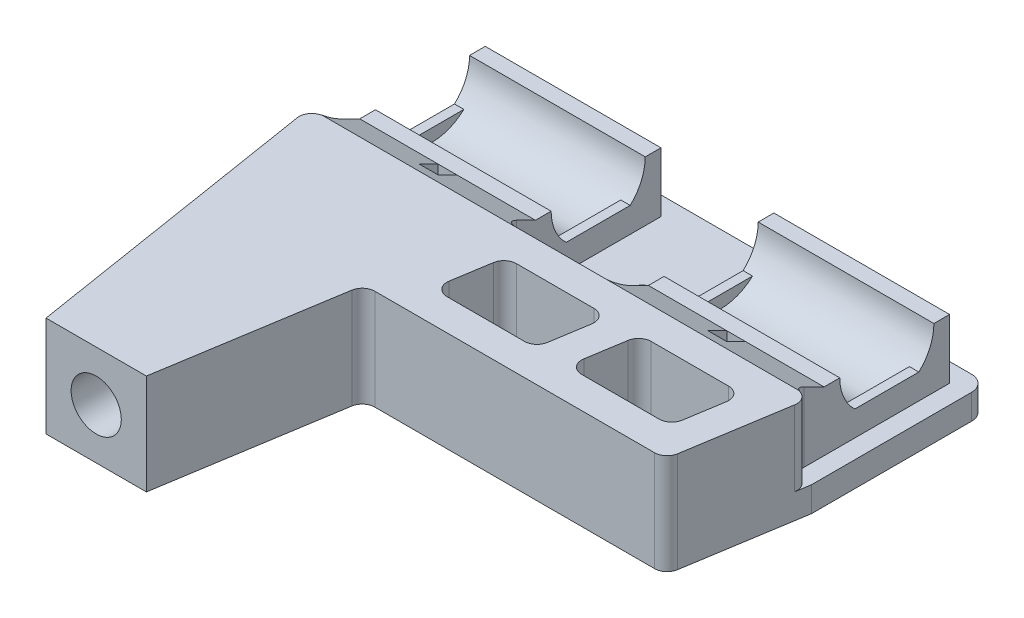
SolidWorks part; units mm, degrees
ref_plane "Front Plane" through (0, 0, 0) normal (0, 0, 1) x (1, 0, 0)
ref_plane "Top Plane" through (0, 0, 0) normal (0, 1, 0) x (1, 0, 0)
ref_plane "Right Plane" through (0, 0, 0) normal (1, 0, 0) x (0, 0, -1)
sketch "Sketch7" plane through (0, 0, 0) normal (0, 1, 0) x (1, 0, 0)
  line L0 (-40, 9) -> (40, 9)
  line L1 (-40, 37) -> (40, 37)
  line L2 (-40, 37) -> (-40, 9)
  line L3 (40, 9) -> (40, 37)
extrude "Extrude2" add sketch "Sketch7" along normal blind 4
sketch "Sketch8" plane through (0, 4, 0) normal (0, 1, 0) x (1, 0, 0)
  line L0 (-40, 66.843) -> (47.0843, 66.843)
  line L1 (-40, 37) -> (-40, 9) construction
  line L3 (-40, 14) -> (46, 14)
  line L4 (-40, 34) -> (46, 34)
  line L5 (-37, 34) -> (-37, 14)
  line L6 (-9, 34) -> (-9, 14)
  line L7 (9, 34) -> (9, 14)
  line L8 (37, 34) -> (37, 14)
extrude "Extrude3" add sketch "Sketch8" along normal blind 9.5 separate body contours L6 region at (-23, 4, -24)
sketch "Sketch10" plane through (-9, 0, 0) normal (1, 0, 0) x (0, 0, -1)
  line L0 (34, 13.5) -> (14, 13.5) construction
  line L1 (24, 13.5) -> (49.4193, 500000)
  line L4 (29.099, 8) -> (18.901, 8)
  circle A0 centre (24, 13.5) radius 7.5
  line M3 (34, 13.5) -> (14, 13.5)
extrude "Extrude6" cut sketch "Sketch10" against normal blind 28 contours A0 L4 M3 region at (-9, 10.906, -24)
ref_plane "Plane3" through (-35.5, 0, 0) normal (-1, 0, 0) x (0, 0, 1)
sketch "Sketch15" plane through (-35.5, 0, 0) normal (-1, 0, 0) x (0, 0, 1)
  circle A0 centre (-24, 13.5) radius 7.5
extrude "Extrude7" cut sketch "Sketch15" against normal blind 25
sketch "Sketch16" plane through (0, 0, -14) normal (0, 0, 1) x (1, 0, 0)
  line L0 (-37, 4) -> (-9, 4) construction
  line L1 (-24.5, 4) -> (-21.5, 4)
  line L3 (-21.5, 7) -> (-21.5, 4)
  line L4 (-21.5, 7) -> (-24.5, 7)
  line L5 (-24.5, 7) -> (-24.5, 4)
ref_plane "Plane4" through (-23, 0, 0) normal (1, 0, 0) x (0, 0, -1)
sketch "Sketch17" plane through (-23, 0, 0) normal (1, 0, 0) x (0, 0, -1)
  circle A0 centre (24, 13.5) radius 12.8062
sweep "Cut-Sweep1" cut profiles "Sketch16" path "Sketch17"
extrude "Extrude8" add sketch "Sketch8<4>" along normal blind 9.5 contours L8 L4 L7 L3 region at (23, 4, -24)
sketch "Sketch8<4>" plane through (0, 4, 0) normal (0, 1, 0) x (1, 0, 0) same geometry as "Sketch8"
sketch "Sketch18" plane through (37, 0, 0) normal (1, 0, 0) x (0, 0, -1)
  line L0 (34, 13.5) -> (14, 13.5) construction
  line L3 (29.099, 8) -> (18.901, 8)
  circle A0 centre (24, 13.5) radius 7.5
  line M3 (34, 13.5) -> (14, 13.5)
extrude "Extrude9" cut sketch "Sketch18" against normal blind 28 contours A0 L3 M3 region at (37, 10.906, -24)
ref_plane "Plane5" through (35.5, 0, 0) normal (1, 0, 0) x (0, 0, -1)
sketch "Sketch19" plane through (35.5, 0, 0) normal (1, 0, 0) x (0, 0, -1)
  circle A0 centre (24, 13.5) radius 7.5
extrude "Extrude10" cut sketch "Sketch19" against normal blind 25
sketch "Sketch20" plane through (0, 0, -14) normal (0, 0, 1) x (1, 0, 0)
  line L0 (21.5, 7) -> (24.5, 7)
  line L1 (9, 4) -> (37, 4) construction
  line L3 (24.5, 7) -> (24.5, 4)
  line L4 (24.5, 4) -> (21.5, 4)
  line L5 (21.5, 4) -> (21.5, 7)
ref_plane "Plane6" through (23, 0, 0) normal (1, 0, 0) x (0, 0, -1)
sketch "Sketch21" plane through (23, 0, 0) normal (1, 0, 0) x (0, 0, -1)
  circle A0 centre (24, 13.5) radius 12.8062
sweep "Cut-Sweep2" cut profiles "Sketch20" path "Sketch21"
fillet "Fillet1" radius 2.5 2 edges at (40, 2, -37) (-40, 2, -37)
sketch "Sketch22" plane through (0, 0, 0) normal (0, 1, 0) x (1, 0, 0)
  line L0 (36.785, -11.0939) -> (40, 9)
  line L1 (12.6682, 4) -> (11.0532, -6.0939)
  line L2 (17.7318, 4) -> (34.1364, 4)
  line L3 (32.5214, -6.0939) -> (16.1168, -6.0939)
  line L4 (40, 9) -> (-40, 9)
  line L5 (-3.7364, 4) -> (-5.3514, -6.0939)
  line L7 (-40, 9) -> (-32, -41)
  line L9 (17.7318, 4) -> (16.1168, -6.0939)
  line L16 (34.1364, 4) -> (32.5214, -6.0939)
  line L17 (-32, -41) -> (-16, -41)
  line L18 (-3.7364, 4) -> (12.6682, 4)
  line L19 (-11.215, -11.0939) -> (36.785, -11.0939)
  line L20 (-16, -41) -> (-11.215, -11.0939)
  line L21 (-5.3514, -6.0939) -> (11.0532, -6.0939)
extrude "Extrude11" add sketch "Sketch22" along normal blind 16
sketch "Sketch25" plane through (0, 4, 0) normal (0, 1, 0) x (-1, 0, 0)
  line L0 (-40, -9) -> (40, -9) construction
  line L1 (37, -14) -> (9, -14)
  line L2 (37, -14) -> (37, -9)
  line L3 (37, -9) -> (9, -9)
  line L4 (9, -14) -> (9, -9)
extrude "Extrude13" add sketch "Sketch25" along normal blind 12
sketch "Sketch26" plane through (-37, 0, 0) normal (-1, 0, 0) x (0, 0, 1)
  line L0 (-14, 13.5) -> (-9, 16)
  line L1 (-9, 16) -> (-14, 16)
  line L2 (-14, 16) -> (-14, 13.5)
extrude "Extrude14" cut sketch "Sketch26" against normal up to next
fillet "Fillet11" radius 2 1 edges at (-9, 10, -9)
sketch "Sketch27" plane through (0, 4, 0) normal (0, 1, 0) x (-1, 0, 0)
  line L1 (-37, -14) -> (-9, -14)
  line L2 (-37, -14) -> (-37, -9)
  line L3 (-37, -9) -> (-9, -9)
  line L4 (-9, -14) -> (-9, -9)
extrude "Extrude15" add sketch "Sketch27" along normal blind 12
sketch "Sketch28" plane through (37, 0, 0) normal (1, 0, 0) x (0, 0, -1)
  line L0 (14, 13.5) -> (9, 16)
  line L1 (9, 16) -> (14, 16)
  line L2 (14, 16) -> (14, 13.5)
extrude "Extrude16" cut sketch "Sketch28" against normal up to next
fillet "Fillet14" radius 2 1 edges at (9, 10, -9)
ref_plane "Plane7" through (0, 16, 0) normal (0, 1, 0) x (-1, 0, 0)
sketch "Sketch30" plane through (0, 16, 0) normal (0, 1, 0) x (-1, 0, 0)
  line L1 (-9, -14) -> (-37, -14) construction
  line L4 (-24.5, -14) -> (-21.5, -14)
  line L5 (-24.5, -14) -> (-24.5, -11)
  line L6 (-24.5, -11) -> (-21.5, -11)
  line L7 (-21.5, -14) -> (-21.5, -11)
extrude "Extrude17" cut sketch "Sketch30" against normal blind 12
sketch "Sketch31" plane through (0, 16, 0) normal (0, 1, 0) x (-1, 0, 0)
  line L1 (37, -14) -> (9, -14) construction
  line L4 (24.5, -14) -> (21.5, -14)
  line L5 (24.5, -14) -> (24.5, -11)
  line L6 (24.5, -11) -> (21.5, -11)
  line L7 (21.5, -14) -> (21.5, -11)
extrude "Extrude18" cut sketch "Sketch31" against normal blind 12
sketch "Sketch32" plane through (0, 0, 41) normal (0, 0, 1) x (1, 0, 0)
  circle A0 centre (-24, 8) radius 4
extrude "Extrude19" cut sketch "Sketch32" against normal blind 40
fillet "Fillet15" radius 2 1 edges tangent propagation no
fillet "Fillet16" radius 2 1 edges at (-37, 10, -9)
fillet "Fillet17" radius 2 1 edges tangent propagation no
fillet "Fillet18" radius 2 1 edges at (37, 10, -9) tangent propagation no
fillet "Fillet19" radius 2 2 edges at (11.0532, 8, 6.0939) (32.5214, 8, 6.0939)
fillet "Fillet20" radius 2 7 edges at (34.1364, 8, -4) (12.6682, 8, -4) (-5.3514, 8, 6.0939) (16.1168, 8, 6.0939) (-3.7364, 8, -4) (36.785, 8, 11.0939) (17.7318, 8, -4)
fillet "Fillet21" radius 2 1 edges at (-11.215, 8, 11.0939)
sketch "Sketch33" plane through (0, 4, 0) normal (0, 1, 0) x (-1, 0, 0)
  circle A0 centre (0, -13.5) radius 1.5
  circle A1 centre (0, -22) radius 1.5
extrude "Extrude20" cut sketch "Sketch33" against normal through all
